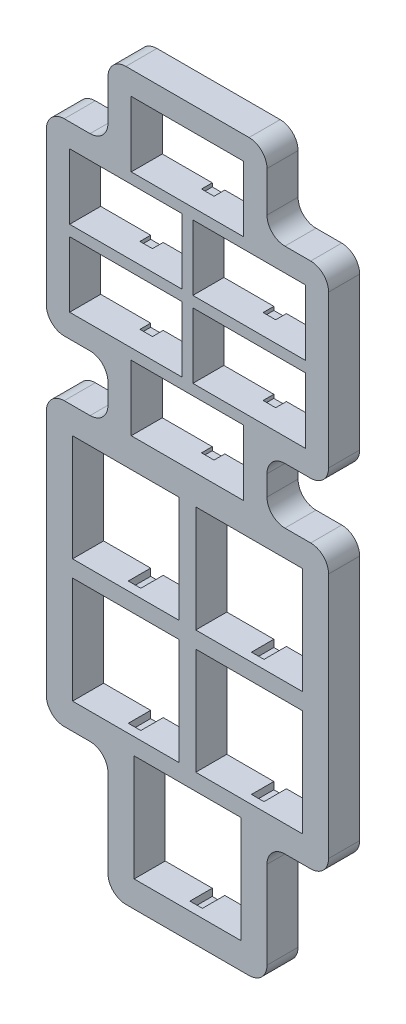
SolidWorks part; units mm, degrees
ref_plane "Front Plane" through (0, 0, 0) normal (0, 0, 1) x (1, 0, 0)
ref_plane "Top Plane" through (0, 0, 0) normal (0, 1, 0) x (1, 0, 0)
ref_plane "Right Plane" through (0, 0, 0) normal (1, 0, 0) x (0, 0, -1)
sketch "Sketch1" plane through (0, 0, 0) normal (0, 0, 1) x (1, 0, 0)
  line L0 (15.1765, -101.5047) -> (15.1765, -87.4077) construction
  line L1 (29.2735, -101.5047) -> (15.1765, -101.5047) construction
  line L2 (29.2735, -101.5047) -> (29.2735, -87.4077) construction
  line L3 (29.2735, -87.4077) -> (15.1765, -87.4077) construction
  line L4 (15.1765, -101.5047) -> (15.1765, -87.4077) construction
  line L5 (29.7815, -102.0127) -> (14.6685, -102.0127)
  line L6 (14.6685, -102.0127) -> (14.6685, -86.8997)
  line L7 (29.7815, -86.8997) -> (14.6685, -86.8997)
  line L8 (20.5423, -84.0423) -> (6.4453, -84.0423) construction
  line L9 (20.5423, -84.0423) -> (20.5423, -69.9453) construction
  line L10 (20.5423, -69.9453) -> (6.4453, -69.9453) construction
  line L11 (6.4453, -84.0423) -> (6.4453, -69.9453) construction
  line L12 (29.7815, -102.0127) -> (29.7815, -86.8997)
  line L13 (21.0503, -84.5503) -> (5.9373, -84.5503)
  line L14 (23.9078, -84.0422) -> (38.0048, -84.0422) construction
  line L15 (23.9078, -84.0422) -> (23.9078, -69.9452) construction
  line L16 (23.9078, -69.9452) -> (38.0048, -69.9452) construction
  line L17 (38.0048, -84.0422) -> (38.0048, -69.9452) construction
  line L18 (5.9373, -84.5503) -> (5.9373, -69.4373)
  line L19 (21.0503, -69.4373) -> (5.9373, -69.4373)
  line L20 (38.0048, -66.5797) -> (23.9078, -66.5797) construction
  line L21 (38.0048, -66.5797) -> (38.0048, -52.4827) construction
  line L22 (38.0048, -52.4827) -> (23.9078, -52.4827) construction
  line L23 (23.9078, -66.5797) -> (23.9078, -52.4827) construction
  line L24 (21.0503, -84.5503) -> (21.0503, -69.4373)
  line L25 (23.3998, -84.5502) -> (38.5128, -84.5502)
  line L26 (20.5423, -66.5798) -> (6.4453, -66.5797) construction
  line L27 (20.5423, -66.5798) -> (20.5423, -52.4827) construction
  line L28 (20.5423, -52.4827) -> (6.4453, -52.4828) construction
  line L29 (6.4453, -66.5797) -> (6.4453, -52.4828) construction
  line L30 (38.5128, -84.5502) -> (38.5128, -69.4372)
  line L31 (23.3998, -69.4372) -> (38.5128, -69.4372)
  line L32 (29.6863, -47.3075) -> (14.7638, -47.3075) construction
  line L33 (29.6863, -47.3075) -> (29.6863, -39.0525) construction
  line L34 (29.6863, -39.0525) -> (14.7638, -39.0525) construction
  line L35 (14.7638, -47.3075) -> (14.7638, -39.0525) construction
  line L36 (23.3998, -84.5502) -> (23.3998, -69.4372)
  line L37 (38.5128, -67.0877) -> (23.3998, -67.0877)
  line L38 (20.955, -36.5125) -> (6.0325, -36.5125) construction
  line L39 (20.955, -36.5125) -> (20.955, -28.2575) construction
  line L40 (20.955, -28.2575) -> (6.0325, -28.2575) construction
  line L41 (6.0325, -36.5125) -> (6.0325, -28.2575) construction
  line L42 (23.3998, -67.0877) -> (23.3998, -51.9747)
  line L43 (38.5128, -51.9747) -> (23.3998, -51.9747)
  line L44 (20.955, -25.7175) -> (6.0325, -25.7175) construction
  line L45 (20.955, -25.7175) -> (20.955, -17.4625) construction
  line L46 (20.955, -17.4625) -> (6.0325, -17.4625) construction
  line L47 (6.0325, -25.7175) -> (6.0325, -17.4625) construction
  line L48 (38.5128, -67.0877) -> (38.5128, -51.9747)
  line L49 (21.0503, -67.0877) -> (5.9373, -67.0877)
  line L50 (29.6863, -14.9225) -> (14.7638, -14.9225) construction
  line L51 (29.6863, -14.9225) -> (29.6863, -6.6675) construction
  line L52 (29.6863, -6.6675) -> (14.7638, -6.6675) construction
  line L53 (14.7638, -14.9225) -> (14.7638, -6.6675) construction
  line L54 (5.9373, -67.0877) -> (5.9373, -51.9747)
  line L55 (21.0503, -51.9747) -> (5.9373, -51.9747)
  line L56 (38.4175, -25.7175) -> (23.495, -25.7175) construction
  line L57 (38.4175, -25.7175) -> (38.4175, -17.4625) construction
  line L58 (38.4175, -17.4625) -> (23.495, -17.4625) construction
  line L59 (23.495, -25.7175) -> (23.495, -17.4625) construction
  line L60 (21.0503, -67.0877) -> (21.0503, -51.9747)
  line L61 (30.1943, -47.8155) -> (14.2558, -47.8155)
  line L62 (38.4175, -36.5125) -> (23.495, -36.5125) construction
  line L63 (38.4175, -36.5125) -> (38.4175, -28.2575) construction
  line L64 (38.4175, -28.2575) -> (23.495, -28.2575) construction
  line L65 (23.495, -36.5125) -> (23.495, -28.2575) construction
  line L66 (14.2558, -47.8155) -> (14.2558, -38.5445)
  line L67 (30.1943, -38.5445) -> (14.2558, -38.5445)
  line L68 (30.1943, -47.8155) -> (30.1943, -38.5445)
  line L69 (21.463, -37.0205) -> (5.5245, -37.0205)
  line L70 (5.5245, -37.0205) -> (5.5245, -27.7495)
  line L71 (21.463, -27.7495) -> (5.5245, -27.7495)
  line L72 (21.463, -37.0205) -> (21.463, -27.7495)
  line L73 (21.463, -26.2255) -> (5.5245, -26.2255)
  line L74 (5.5245, -26.2255) -> (5.5245, -16.9545)
  line L75 (21.463, -16.9545) -> (5.5245, -16.9545)
  line L76 (21.463, -26.2255) -> (21.463, -16.9545)
  line L77 (30.1943, -15.4305) -> (14.2558, -15.4305)
  line L78 (14.2558, -15.4305) -> (14.2558, -6.1595)
  line L79 (30.1943, -6.1595) -> (14.2558, -6.1595)
  line L80 (30.1943, -15.4305) -> (30.1943, -6.1595)
  line L81 (38.9255, -26.2255) -> (22.987, -26.2255)
  line L82 (22.987, -26.2255) -> (22.987, -16.9545)
  line L83 (38.9255, -16.9545) -> (22.987, -16.9545)
  line L84 (38.9255, -26.2255) -> (38.9255, -16.9545)
  line L85 (38.9255, -37.0205) -> (22.987, -37.0205)
  line L86 (22.987, -37.0205) -> (22.987, -27.7495)
  line L87 (38.9255, -27.7495) -> (22.987, -27.7495)
  line L88 (38.9255, -37.0205) -> (38.9255, -27.7495)
  line L97 (30.9563, -85.725) -> (39.6875, -85.725)
  line L98 (39.6875, -85.725) -> (39.6875, -50.8)
  line L99 (39.6875, -50.8) -> (4.7625, -50.8)
  line L100 (4.7625, -50.8) -> (4.7625, -85.725)
  line L101 (30.9563, -37.7825) -> (39.6875, -37.7825)
  line L102 (39.6875, -37.7825) -> (39.6875, -16.1925)
  line L103 (39.6875, -16.1925) -> (30.9563, -16.1925)
  line L104 (30.9563, -16.1925) -> (30.9563, -5.3975)
  line L105 (30.9563, -5.3975) -> (13.4938, -5.3975)
  line L106 (13.4938, -5.3975) -> (13.4938, -16.1925)
  line L107 (13.4938, -16.1925) -> (4.7625, -16.1925)
  line L108 (4.7625, -16.1925) -> (4.7625, -37.7825)
  line L109 (4.7625, -37.7825) -> (13.4938, -37.7825)
  line L110 (13.4938, -37.7825) -> (13.4938, -48.5775)
  line L111 (13.4938, -48.5775) -> (30.9563, -48.5775)
  line L112 (30.9563, -48.5775) -> (30.9563, -37.7825)
  line L113 (30.9563, -37.7825) -> (39.6875, -37.7825)
  line L114 (39.6875, -37.7825) -> (39.6875, -16.1925)
  line L115 (39.6875, -16.1925) -> (30.9563, -16.1925)
  line L116 (30.9563, -16.1925) -> (30.9563, -5.3975)
  line L117 (30.9563, -5.3975) -> (13.4938, -5.3975)
  line L118 (13.4938, -5.3975) -> (13.4938, -16.1925)
  line L119 (13.4938, -16.1925) -> (4.7625, -16.1925)
  line L120 (4.7625, -16.1925) -> (4.7625, -37.7825)
  line L121 (4.7625, -37.7825) -> (13.4938, -37.7825)
  line L122 (13.4938, -37.7825) -> (13.4938, -48.5775)
  line L124 (30.9563, -48.5775) -> (30.9563, -37.7825)
  line L125 (4.7625, -85.725) -> (13.4938, -85.725)
  line L126 (13.4938, -85.725) -> (13.4938, -103.1875)
  line L127 (13.4938, -103.1875) -> (30.9563, -103.1875)
  line L128 (30.9563, -103.1875) -> (30.9563, -85.725)
  line L129 (30.9563, -85.725) -> (39.6875, -85.725)
  line L130 (39.6875, -85.725) -> (39.6875, -50.8)
  line L131 (39.6875, -50.8) -> (30.9563, -50.8)
  line L132 (4.7625, -50.8) -> (4.7625, -85.725)
  line L133 (4.7625, -85.725) -> (13.4938, -85.725)
  line L134 (13.4938, -85.725) -> (13.4938, -103.1875)
  line L135 (13.4938, -103.1875) -> (30.9563, -103.1875)
  line L136 (30.9563, -103.1875) -> (30.9563, -85.725)
  line L2229 (13.4938, -50.8) -> (4.7625, -50.8)
  line L2231 (30.9563, -48.5775) -> (30.9563, -50.8)
  line L2233 (13.4938, -48.5775) -> (13.4938, -50.8)
  dimension "D1" = 0.508
  dimension "D2" = 0
  dimension "D3" = 0
extrude "Boss-Extrude1" add sketch "Sketch1" against normal up to surface (4.4025 mm away)
sketch "Sketch4" plane through (0, 0, -4.4025) normal (0, 0, -1) x (-1, 0, 0)
  line L40 (-30.9563, -37.7825) -> (-30.9563, -50.8)
  line L41 (-30.9563, -50.8) -> (-39.6875, -50.8)
  line L42 (-39.6875, -50.8) -> (-39.6875, -85.725)
  line L43 (-39.6875, -85.725) -> (-30.9563, -85.725)
  line L44 (-30.9563, -85.725) -> (-30.9563, -103.1875)
  line L45 (-30.9563, -103.1875) -> (-13.4938, -103.1875)
  line L46 (-13.4938, -103.1875) -> (-13.4938, -85.725)
  line L47 (-13.4938, -85.725) -> (-4.7625, -85.725)
  line L48 (-4.7625, -85.725) -> (-4.7625, -50.8)
  line L49 (-4.7625, -50.8) -> (-13.4938, -50.8)
  line L50 (-13.4938, -50.8) -> (-13.4938, -37.7825)
  line L51 (-13.4938, -37.7825) -> (-4.7625, -37.7825)
  line L52 (-4.7625, -37.7825) -> (-4.7625, -16.1925)
  line L53 (-4.7625, -16.1925) -> (-13.4938, -16.1925)
  line L54 (-13.4938, -16.1925) -> (-13.4938, -5.3975)
  line L55 (-13.4938, -5.3975) -> (-30.9563, -5.3975)
  line L56 (-30.9563, -5.3975) -> (-30.9563, -16.1925)
  line L57 (-30.9563, -16.1925) -> (-39.6875, -16.1925)
  line L58 (-39.6875, -16.1925) -> (-39.6875, -37.7825)
  line L59 (-39.6875, -37.7825) -> (-30.9563, -37.7825)
  line L60 (-30.9563, -37.7825) -> (-30.9563, -50.8)
  line L61 (-30.9563, -50.8) -> (-39.6875, -50.8)
  line L62 (-39.6875, -50.8) -> (-39.6875, -85.725)
  line L63 (-39.6875, -85.725) -> (-30.9563, -85.725)
  line L64 (-30.9563, -85.725) -> (-30.9563, -103.1875)
  line L65 (-30.9563, -103.1875) -> (-13.4938, -103.1875)
  line L66 (-13.4938, -103.1875) -> (-13.4938, -85.725)
  line L67 (-13.4938, -85.725) -> (-4.7625, -85.725)
  line L68 (-4.7625, -85.725) -> (-4.7625, -50.8)
  line L69 (-4.7625, -50.8) -> (-13.4938, -50.8)
  line L70 (-13.4938, -50.8) -> (-13.4938, -37.7825)
  line L71 (-13.4938, -37.7825) -> (-4.7625, -37.7825)
  line L72 (-4.7625, -37.7825) -> (-4.7625, -16.1925)
  line L73 (-4.7625, -16.1925) -> (-13.4938, -16.1925)
  line L74 (-13.4938, -16.1925) -> (-13.4938, -5.3975)
  line L75 (-13.4938, -5.3975) -> (-30.9563, -5.3975)
  line L76 (-30.9563, -5.3975) -> (-30.9563, -16.1925)
  line L77 (-30.9563, -16.1925) -> (-39.6875, -16.1925)
  line L78 (-39.6875, -16.1925) -> (-39.6875, -37.7825)
  line L79 (-39.6875, -37.7825) -> (-30.9563, -37.7825)
  dimension "D1" = 0
extrude "Extrude-Thin1" add sketch "Sketch4" against normal through all thin thin type one direction wall 2.54
fillet "Fillet1" radius 2.54 20 edges at (42.2275, -48.26, -2.2012) (2.2225, -13.6525, -2.2012) (10.9538, -2.8575, -2.2012) (33.4963, -2.8575, -2.2012) (42.2275, -13.6525, -2.2012) (42.2275, -40.3225, -2.2012) (2.2225, -40.3225, -2.2012) (2.2225, -48.26, -2.2012) (42.2275, -88.265, -2.2012) (33.4963, -105.7275, -2.2012) (10.9538, -105.7275, -2.2012) (2.2225, -88.265, -2.2012) (10.9538, -88.265, -2.2012) (33.4963, -88.265, -2.2012) (33.4963, -40.3225, -2.2012) (33.4963, -48.26, -2.2012) (10.9538, -48.26, -2.2012) (10.9538, -40.3225, -2.2012) (10.9538, -13.6525, -2.2012) (33.4963, -13.6525, -2.2012)
sketch "Sketch5" plane through (0, 0, -4.4025) normal (0, 0, -1) x (-1, 0, 0)
  line L0 (-14.2558, -6.1595) -> (-30.1943, -6.1595) construction
  line L1 (-26.5906, -6.1595) -> (-25.3206, -6.1595) construction
  line L2 (-26.5906, -6.1595) -> (-26.5906, -5.9065) construction
  line L3 (-26.5906, -5.9065) -> (-25.3206, -5.9065) construction
  line L4 (-25.3206, -6.1595) -> (-25.3206, -5.9065) construction
  line L5 (-19.1294, -6.1595) -> (-17.8594, -6.1595) construction
  line L6 (-19.1294, -6.1595) -> (-19.1294, -5.9065) construction
  line L7 (-19.1294, -5.9065) -> (-17.8594, -5.9065) construction
  line L8 (-17.8594, -6.1595) -> (-17.8594, -5.9065) construction
  line L9 (-21.59, -15.6835) -> (-21.59, -15.4305) construction
  line L10 (-22.86, -15.6835) -> (-21.59, -15.6835) construction
  line L11 (-22.86, -15.6835) -> (-22.86, -15.4305) construction
  line L12 (-22.86, -15.4305) -> (-21.59, -15.4305) construction
  line L13 (-35.3219, -16.7015) -> (-34.0519, -16.7015) construction
  line L14 (-27.8606, -16.7015) -> (-26.5906, -16.7015) construction
  line L15 (-30.3213, -26.4785) -> (-30.3213, -26.2255) construction
  line L16 (-31.5913, -26.4785) -> (-30.3213, -26.4785) construction
  line L17 (-35.3219, -16.9545) -> (-34.0519, -16.9545) construction
  line L18 (-34.0519, -16.9545) -> (-34.0519, -16.7015) construction
  line L19 (-27.8606, -16.9545) -> (-26.5906, -16.9545) construction
  line L20 (-26.5906, -16.9545) -> (-26.5906, -16.7015) construction
  line L21 (-31.5913, -26.2255) -> (-30.3213, -26.2255) construction
  line L22 (-27.8606, -16.9545) -> (-27.8606, -16.7015) construction
  line L23 (-31.5913, -26.4785) -> (-31.5913, -26.2255) construction
  line L24 (-35.3219, -16.9545) -> (-35.3219, -16.7015) construction
  line L25 (-12.8588, -26.4785) -> (-12.8588, -26.2255) construction
  line L26 (-16.5894, -16.9545) -> (-16.5894, -16.7015) construction
  line L27 (-10.3981, -16.9545) -> (-10.3981, -16.7015) construction
  line L28 (-14.1288, -26.4785) -> (-12.8588, -26.4785) construction
  line L29 (-14.1288, -26.4785) -> (-14.1288, -26.2255) construction
  line L30 (-17.8594, -16.7015) -> (-16.5894, -16.7015) construction
  line L31 (-9.1281, -16.9545) -> (-9.1281, -16.7015) construction
  line L32 (-14.1288, -26.2255) -> (-12.8588, -26.2255) construction
  line L33 (-17.8594, -16.9545) -> (-16.5894, -16.9545) construction
  line L34 (-10.3981, -16.9545) -> (-9.1281, -16.9545) construction
  line L35 (-17.8594, -16.9545) -> (-17.8594, -16.7015) construction
  line L36 (-10.3981, -16.7015) -> (-9.1281, -16.7015) construction
  line L37 (-30.3213, -37.2735) -> (-30.3213, -37.0205) construction
  line L38 (-31.5913, -37.2735) -> (-31.5913, -37.0205) construction
  line L39 (-27.8606, -27.7495) -> (-26.5906, -27.7495) construction
  line L40 (-10.3981, -27.7495) -> (-10.3981, -27.4965) construction
  line L41 (-17.8594, -27.4965) -> (-16.5894, -27.4965) construction
  line L42 (-31.5913, -37.0205) -> (-30.3213, -37.0205) construction
  line L43 (-14.1287, -37.2735) -> (-12.8587, -37.2735) construction
  line L44 (-35.3219, -27.4965) -> (-34.0519, -27.4965) construction
  line L45 (-31.5913, -37.2735) -> (-30.3213, -37.2735) construction
  line L46 (-12.8587, -37.2735) -> (-12.8587, -37.0205) construction
  line L47 (-26.5906, -27.7495) -> (-26.5906, -27.4965) construction
  line L48 (-9.1281, -27.7495) -> (-9.1281, -27.4965) construction
  line L49 (-16.5894, -27.7495) -> (-16.5894, -27.4965) construction
  line L50 (-17.8594, -27.7495) -> (-16.5894, -27.7495) construction
  line L51 (-27.8606, -27.7495) -> (-27.8606, -27.4965) construction
  line L52 (-10.3981, -27.7495) -> (-9.1281, -27.7495) construction
  line L53 (-34.0519, -27.7495) -> (-34.0519, -27.4965) construction
  line L54 (-35.3219, -27.7495) -> (-35.3219, -27.4965) construction
  line L55 (-17.8594, -27.7495) -> (-17.8594, -27.4965) construction
  line L56 (-35.3219, -27.7495) -> (-34.0519, -27.7495) construction
  line L57 (-14.1287, -37.2735) -> (-14.1287, -37.0205) construction
  line L58 (-14.1287, -37.0205) -> (-12.8587, -37.0205) construction
  line L59 (-27.8606, -27.4965) -> (-26.5906, -27.4965) construction
  line L60 (-10.3981, -27.4965) -> (-9.1281, -27.4965) construction
  line L61 (-22.86, -47.8155) -> (-21.59, -47.8155) construction
  line L62 (-26.5906, -38.5445) -> (-26.5906, -38.2915) construction
  line L63 (-21.59, -48.0685) -> (-21.59, -47.8155) construction
  line L64 (-25.3206, -38.5445) -> (-25.3206, -38.2915) construction
  line L65 (-22.86, -48.0685) -> (-21.59, -48.0685) construction
  line L66 (-19.1294, -38.5445) -> (-17.8594, -38.5445) construction
  line L67 (-19.1294, -38.2915) -> (-17.8594, -38.2915) construction
  line L68 (-26.5906, -38.5445) -> (-25.3206, -38.5445) construction
  line L69 (-22.86, -48.0685) -> (-22.86, -47.8155) construction
  line L70 (-19.1294, -38.5445) -> (-19.1294, -38.2915) construction
  line L71 (-17.8594, -38.5445) -> (-17.8594, -38.2915) construction
  line L72 (-26.5906, -38.2915) -> (-25.3206, -38.2915) construction
  line L73 (-26.8446, -6.4135) -> (-25.0666, -6.4135)
  line L74 (-25.0666, -6.4135) -> (-25.0666, -5.6525)
  line L75 (-26.8446, -5.6525) -> (-25.0666, -5.6525)
  line L76 (-26.8446, -6.4135) -> (-26.8446, -5.6525)
  line L77 (-19.3834, -6.4135) -> (-17.6054, -6.4135)
  line L78 (-17.6054, -6.4135) -> (-17.6054, -5.6525)
  line L79 (-19.3834, -5.6525) -> (-17.6054, -5.6525)
  line L80 (-19.3834, -6.4135) -> (-19.3834, -5.6525)
  line L81 (-21.336, -15.9375) -> (-21.336, -15.1765)
  line L82 (-23.114, -15.1765) -> (-21.336, -15.1765)
  line L83 (-23.114, -15.9375) -> (-23.114, -15.1765)
  line L84 (-23.114, -15.9375) -> (-21.336, -15.9375)
  line L85 (-35.5759, -16.4475) -> (-33.7979, -16.4475)
  line L86 (-33.7979, -17.2085) -> (-33.7979, -16.4475)
  line L87 (-35.5759, -17.2085) -> (-33.7979, -17.2085)
  line L88 (-35.5759, -17.2085) -> (-35.5759, -16.4475)
  line L89 (-28.1146, -16.4475) -> (-26.3366, -16.4475)
  line L90 (-26.3366, -17.2085) -> (-26.3366, -16.4475)
  line L91 (-28.1146, -17.2085) -> (-26.3366, -17.2085)
  line L92 (-28.1146, -17.2085) -> (-28.1146, -16.4475)
  line L93 (-30.0673, -26.7325) -> (-30.0673, -25.9715)
  line L94 (-31.8453, -25.9715) -> (-30.0673, -25.9715)
  line L95 (-31.8453, -26.7325) -> (-31.8453, -25.9715)
  line L96 (-31.8453, -26.7325) -> (-30.0673, -26.7325)
  line L97 (-12.6048, -26.7325) -> (-12.6048, -25.9715)
  line L98 (-14.3828, -25.9715) -> (-12.6048, -25.9715)
  line L99 (-14.3828, -26.7325) -> (-14.3828, -25.9715)
  line L100 (-14.3828, -26.7325) -> (-12.6048, -26.7325)
  line L101 (-16.3354, -17.2085) -> (-16.3354, -16.4475)
  line L102 (-18.1134, -16.4475) -> (-16.3354, -16.4475)
  line L103 (-18.1134, -17.2085) -> (-18.1134, -16.4475)
  line L104 (-18.1134, -17.2085) -> (-16.3354, -17.2085)
  line L105 (-10.6521, -17.2085) -> (-10.6521, -16.4475)
  line L106 (-10.6521, -16.4475) -> (-8.8741, -16.4475)
  line L107 (-8.8741, -17.2085) -> (-8.8741, -16.4475)
  line L108 (-10.6521, -17.2085) -> (-8.8741, -17.2085)
  line L109 (-30.0673, -37.5275) -> (-30.0673, -36.7665)
  line L110 (-31.8453, -36.7665) -> (-30.0673, -36.7665)
  line L111 (-31.8453, -37.5275) -> (-31.8453, -36.7665)
  line L112 (-31.8453, -37.5275) -> (-30.0673, -37.5275)
  line L113 (-28.1146, -28.0035) -> (-26.3366, -28.0035)
  line L114 (-26.3366, -28.0035) -> (-26.3366, -27.2425)
  line L115 (-28.1146, -27.2425) -> (-26.3366, -27.2425)
  line L116 (-28.1146, -28.0035) -> (-28.1146, -27.2425)
  line L117 (-10.6521, -28.0035) -> (-10.6521, -27.2425)
  line L118 (-10.6521, -27.2425) -> (-8.8741, -27.2425)
  line L119 (-8.8741, -28.0035) -> (-8.8741, -27.2425)
  line L120 (-10.6521, -28.0035) -> (-8.8741, -28.0035)
  line L121 (-18.1134, -27.2425) -> (-16.3354, -27.2425)
  line L122 (-16.3354, -28.0035) -> (-16.3354, -27.2425)
  line L123 (-18.1134, -28.0035) -> (-16.3354, -28.0035)
  line L124 (-18.1134, -28.0035) -> (-18.1134, -27.2425)
  line L125 (-14.3827, -37.5275) -> (-12.6047, -37.5275)
  line L126 (-12.6047, -37.5275) -> (-12.6047, -36.7665)
  line L127 (-14.3827, -36.7665) -> (-12.6047, -36.7665)
  line L128 (-14.3827, -37.5275) -> (-14.3827, -36.7665)
  line L129 (-35.5759, -27.2425) -> (-33.7979, -27.2425)
  line L130 (-33.7979, -28.0035) -> (-33.7979, -27.2425)
  line L131 (-35.5759, -28.0035) -> (-33.7979, -28.0035)
  line L132 (-35.5759, -28.0035) -> (-35.5759, -27.2425)
  line L133 (-23.114, -47.5615) -> (-21.336, -47.5615)
  line L134 (-21.336, -48.3225) -> (-21.336, -47.5615)
  line L135 (-23.114, -48.3225) -> (-21.336, -48.3225)
  line L136 (-23.114, -48.3225) -> (-23.114, -47.5615)
  line L137 (-26.8446, -38.7985) -> (-26.8446, -38.0375)
  line L138 (-26.8446, -38.0375) -> (-25.0666, -38.0375)
  line L139 (-25.0666, -38.7985) -> (-25.0666, -38.0375)
  line L140 (-26.8446, -38.7985) -> (-25.0666, -38.7985)
  line L141 (-19.3834, -38.7985) -> (-17.6054, -38.7985)
  line L142 (-17.6054, -38.7985) -> (-17.6054, -38.0375)
  line L143 (-19.3834, -38.0375) -> (-17.6054, -38.0375)
  line L144 (-19.3834, -38.7985) -> (-19.3834, -38.0375)
  dimension "D1" = 0.254
extrude "Cut-Extrude1" cut sketch "Sketch5" against normal blind 1.524
sketch "Sketch6" plane through (0, 0, -4.4025) normal (0, 0, -1) x (-1, 0, 0)
  line L0 (-23.3998, -51.9747) -> (-38.5128, -51.9747) construction
  line L1 (-35.1155, -51.9747) -> (-33.8455, -51.9747) construction
  line L2 (-35.1155, -51.9747) -> (-35.1155, -51.2127) construction
  line L3 (-35.1155, -51.2127) -> (-33.8455, -51.2127) construction
  line L4 (-33.8455, -51.9747) -> (-33.8455, -51.2127) construction
  line L5 (-28.067, -51.9747) -> (-28.067, -51.2127) construction
  line L6 (-28.067, -51.2127) -> (-26.797, -51.2127) construction
  line L7 (-28.067, -51.9747) -> (-26.797, -51.9747) construction
  line L8 (-26.797, -51.9747) -> (-26.797, -51.2127) construction
  line L9 (-30.3213, -67.8497) -> (-30.3213, -67.0877) construction
  line L10 (-31.5913, -67.8497) -> (-31.5913, -67.0877) construction
  line L11 (-31.5913, -67.0877) -> (-30.3213, -67.0877) construction
  line L12 (-31.5913, -67.8497) -> (-30.3213, -67.8497) construction
  line L13 (-10.6045, -51.9748) -> (-10.6045, -51.2128) construction
  line L14 (-12.8588, -67.8498) -> (-12.8588, -67.0878) construction
  line L15 (-17.653, -51.9748) -> (-17.653, -51.2128) construction
  line L16 (-16.383, -51.9748) -> (-16.383, -51.2128) construction
  line L17 (-10.6045, -51.9748) -> (-9.3345, -51.9748) construction
  line L18 (-9.3345, -51.9748) -> (-9.3345, -51.2128) construction
  line L19 (-10.6045, -51.2128) -> (-9.3345, -51.2128) construction
  line L20 (-14.1288, -67.8498) -> (-12.8588, -67.8498) construction
  line L21 (-17.653, -51.9748) -> (-16.383, -51.9748) construction
  line L22 (-14.1288, -67.8498) -> (-14.1288, -67.0878) construction
  line L23 (-17.653, -51.2128) -> (-16.383, -51.2128) construction
  line L24 (-14.1288, -67.0878) -> (-12.8588, -67.0878) construction
  line L25 (-30.3213, -85.3122) -> (-30.3213, -84.5502) construction
  line L26 (-31.5913, -85.3122) -> (-30.3213, -85.3122) construction
  line L27 (-14.1288, -84.5503) -> (-12.8588, -84.5503) construction
  line L28 (-35.1155, -69.4372) -> (-33.8455, -69.4372) construction
  line L29 (-9.3345, -69.4373) -> (-9.3345, -68.6753) construction
  line L30 (-35.1155, -68.6752) -> (-33.8455, -68.6752) construction
  line L31 (-17.653, -69.4373) -> (-16.383, -69.4373) construction
  line L32 (-17.653, -68.6753) -> (-16.383, -68.6753) construction
  line L33 (-28.067, -68.6752) -> (-26.797, -68.6752) construction
  line L34 (-17.653, -69.4373) -> (-17.653, -68.6753) construction
  line L35 (-35.1155, -69.4372) -> (-35.1155, -68.6752) construction
  line L36 (-31.5913, -85.3122) -> (-31.5913, -84.5502) construction
  line L37 (-12.8588, -85.3123) -> (-12.8588, -84.5503) construction
  line L38 (-28.067, -69.4372) -> (-26.797, -69.4372) construction
  line L39 (-14.1288, -85.3123) -> (-12.8588, -85.3123) construction
  line L40 (-16.383, -69.4373) -> (-16.383, -68.6753) construction
  line L41 (-31.5913, -84.5502) -> (-30.3213, -84.5502) construction
  line L42 (-33.8455, -69.4372) -> (-33.8455, -68.6752) construction
  line L43 (-28.067, -69.4372) -> (-28.067, -68.6752) construction
  line L44 (-26.797, -69.4372) -> (-26.797, -68.6752) construction
  line L45 (-10.6045, -69.4373) -> (-9.3345, -69.4373) construction
  line L46 (-14.1288, -85.3123) -> (-14.1288, -84.5503) construction
  line L47 (-10.6045, -68.6753) -> (-9.3345, -68.6753) construction
  line L48 (-10.6045, -69.4373) -> (-10.6045, -68.6753) construction
  line L49 (-26.3843, -86.8997) -> (-25.1143, -86.8997) construction
  line L50 (-21.59, -102.7747) -> (-21.59, -102.0127) construction
  line L51 (-22.86, -102.7747) -> (-22.86, -102.0127) construction
  line L52 (-26.3843, -86.1377) -> (-25.1143, -86.1377) construction
  line L53 (-22.86, -102.7747) -> (-21.59, -102.7747) construction
  line L54 (-22.86, -102.0127) -> (-21.59, -102.0127) construction
  line L55 (-19.3358, -86.1377) -> (-18.0658, -86.1377) construction
  line L56 (-26.3843, -86.8997) -> (-26.3843, -86.1377) construction
  line L57 (-25.1143, -86.8997) -> (-25.1143, -86.1377) construction
  line L58 (-18.0658, -86.8997) -> (-18.0658, -86.1377) construction
  line L59 (-19.3358, -86.8997) -> (-19.3358, -86.1377) construction
  line L60 (-19.3358, -86.8997) -> (-18.0658, -86.8997) construction
  line L61 (-35.3695, -52.2287) -> (-33.5915, -52.2287)
  line L62 (-33.5915, -52.2287) -> (-33.5915, -50.9587)
  line L63 (-35.3695, -50.9587) -> (-33.5915, -50.9587)
  line L64 (-35.3695, -52.2287) -> (-35.3695, -50.9587)
  line L65 (-28.321, -52.2287) -> (-28.321, -50.9587)
  line L66 (-28.321, -50.9587) -> (-26.543, -50.9587)
  line L67 (-26.543, -52.2287) -> (-26.543, -50.9587)
  line L68 (-28.321, -52.2287) -> (-26.543, -52.2287)
  line L69 (-30.0673, -68.1037) -> (-30.0673, -66.8337)
  line L70 (-31.8453, -66.8337) -> (-30.0673, -66.8337)
  line L71 (-31.8453, -68.1037) -> (-31.8453, -66.8337)
  line L72 (-31.8453, -68.1037) -> (-30.0673, -68.1037)
  line L73 (-10.8585, -52.2288) -> (-10.8585, -50.9588)
  line L74 (-10.8585, -50.9588) -> (-9.0805, -50.9588)
  line L75 (-9.0805, -52.2288) -> (-9.0805, -50.9588)
  line L76 (-10.8585, -52.2288) -> (-9.0805, -52.2288)
  line L77 (-12.6048, -68.1038) -> (-12.6048, -66.8338)
  line L78 (-14.3828, -66.8338) -> (-12.6048, -66.8338)
  line L79 (-14.3828, -68.1038) -> (-14.3828, -66.8338)
  line L80 (-14.3828, -68.1038) -> (-12.6048, -68.1038)
  line L81 (-17.907, -52.2288) -> (-17.907, -50.9588)
  line L82 (-17.907, -50.9588) -> (-16.129, -50.9588)
  line L83 (-16.129, -52.2288) -> (-16.129, -50.9588)
  line L84 (-17.907, -52.2288) -> (-16.129, -52.2288)
  line L85 (-30.0673, -85.5662) -> (-30.0673, -84.2962)
  line L86 (-31.8453, -84.2962) -> (-30.0673, -84.2962)
  line L87 (-31.8453, -85.5662) -> (-31.8453, -84.2962)
  line L88 (-31.8453, -85.5662) -> (-30.0673, -85.5662)
  line L89 (-14.3828, -84.2963) -> (-12.6048, -84.2963)
  line L90 (-12.6048, -85.5663) -> (-12.6048, -84.2963)
  line L91 (-14.3828, -85.5663) -> (-12.6048, -85.5663)
  line L92 (-14.3828, -85.5663) -> (-14.3828, -84.2963)
  line L93 (-35.3695, -69.6912) -> (-33.5915, -69.6912)
  line L94 (-33.5915, -69.6912) -> (-33.5915, -68.4212)
  line L95 (-35.3695, -68.4212) -> (-33.5915, -68.4212)
  line L96 (-35.3695, -69.6912) -> (-35.3695, -68.4212)
  line L97 (-9.0805, -69.6913) -> (-9.0805, -68.4213)
  line L98 (-10.8585, -68.4213) -> (-9.0805, -68.4213)
  line L99 (-10.8585, -69.6913) -> (-10.8585, -68.4213)
  line L100 (-10.8585, -69.6913) -> (-9.0805, -69.6913)
  line L101 (-17.907, -69.6913) -> (-16.129, -69.6913)
  line L102 (-16.129, -69.6913) -> (-16.129, -68.4213)
  line L103 (-17.907, -68.4213) -> (-16.129, -68.4213)
  line L104 (-17.907, -69.6913) -> (-17.907, -68.4213)
  line L105 (-28.321, -68.4212) -> (-26.543, -68.4212)
  line L106 (-26.543, -69.6912) -> (-26.543, -68.4212)
  line L107 (-28.321, -69.6912) -> (-26.543, -69.6912)
  line L108 (-28.321, -69.6912) -> (-28.321, -68.4212)
  line L109 (-26.6383, -87.1537) -> (-24.8603, -87.1537)
  line L110 (-24.8603, -87.1537) -> (-24.8603, -85.8837)
  line L111 (-26.6383, -85.8837) -> (-24.8603, -85.8837)
  line L112 (-26.6383, -87.1537) -> (-26.6383, -85.8837)
  line L113 (-21.336, -103.0287) -> (-21.336, -101.7587)
  line L114 (-23.114, -101.7587) -> (-21.336, -101.7587)
  line L115 (-23.114, -103.0287) -> (-23.114, -101.7587)
  line L116 (-23.114, -103.0287) -> (-21.336, -103.0287)
  line L117 (-19.5898, -85.8837) -> (-17.8118, -85.8837)
  line L118 (-17.8118, -87.1537) -> (-17.8118, -85.8837)
  line L119 (-19.5898, -87.1537) -> (-17.8118, -87.1537)
  line L120 (-19.5898, -87.1537) -> (-19.5898, -85.8837)
  point P7 (-34.0995, -51.2127)
  point P11 (-27.051, -51.2127)
  point P16 (-30.5753, -67.0877)
  point P22 (-16.637, -51.2128)
  point P26 (-9.5885, -51.2128)
  point P31 (-13.1128, -67.0878)
  point P37 (-34.0995, -68.6752)
  point P41 (-27.051, -68.6752)
  point P46 (-30.5753, -84.5502)
  point P52 (-16.637, -68.6753)
  point P56 (-9.5885, -68.6753)
  point P61 (-13.1128, -84.5503)
  point P67 (-25.3683, -86.1377)
  point P71 (-18.3198, -86.1377)
  point P76 (-21.844, -102.0127)
  dimension "D1" = 0.254
extrude "Cut-Extrude2" cut sketch "Sketch6" against normal blind 3.175
